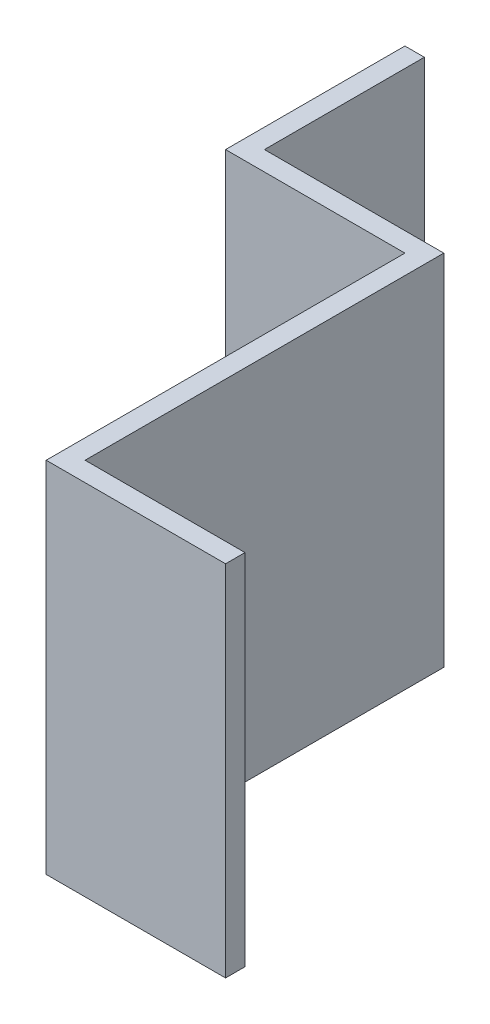
SolidWorks part; units mm, degrees
material "Galvanized Steel"
ref_plane "Front Plane" through (0, 0, 0) normal (0, 0, 1) x (1, 0, 0)
ref_plane "Top Plane" through (0, 0, 0) normal (0, 1, 0) x (1, 0, 0)
ref_plane "Right Plane" through (0, 0, 0) normal (1, 0, 0) x (0, 0, -1)
sketch "Sketch1" plane through (0, 0, 0) normal (0, 1, 0) x (1, 0, 0)
  line L0 (-9.9466, 28.1534) -> (15.4534, 28.1534)
  line L1 (-12.7, -25.4) -> (12.7, -25.4) construction
  line L2 (-12.7, -25.4) -> (-12.7, 25.4) construction
  line L3 (-12.7, 25.4) -> (12.7, 25.4)
  line L4 (12.7, -25.4) -> (12.7, 25.4)
  line L5 (-12.7, -25.4) -> (12.7, 25.4) construction
  line L6 (-12.7, 25.4) -> (12.7, -25.4) construction
  line L8 (-12.7, 25.4) -> (-12.7, 50.8)
  line L9 (-12.7, 50.8) -> (-9.9466, 50.8)
  line L10 (-9.9466, 28.1534) -> (-9.9466, 50.8)
  line L11 (12.7, -25.4) -> (38.1, -25.4)
  line L13 (15.4534, -22.6466) -> (38.1, -22.6466)
  line L14 (38.1, -25.4) -> (38.1, -22.6466)
  line L15 (15.4534, -22.6466) -> (15.4534, 28.1534)
  line L16 (15.4534, -25.4) -> (15.4534, 28.1534) construction
  line L17 (-12.7, 28.1534) -> (15.4534, 28.1534) construction
  line L18 (-9.9466, 28.1534) -> (-9.9466, 25.4) construction
  point P0 (0, 0)
  dimension "D1" = 25.4
  dimension "D2" = 2.7534
  dimension "D3" = 50.8
  dimension "D4" = 25.4
extrude "Boss-Extrude1" add sketch "Sketch1" along normal blind 50.8
